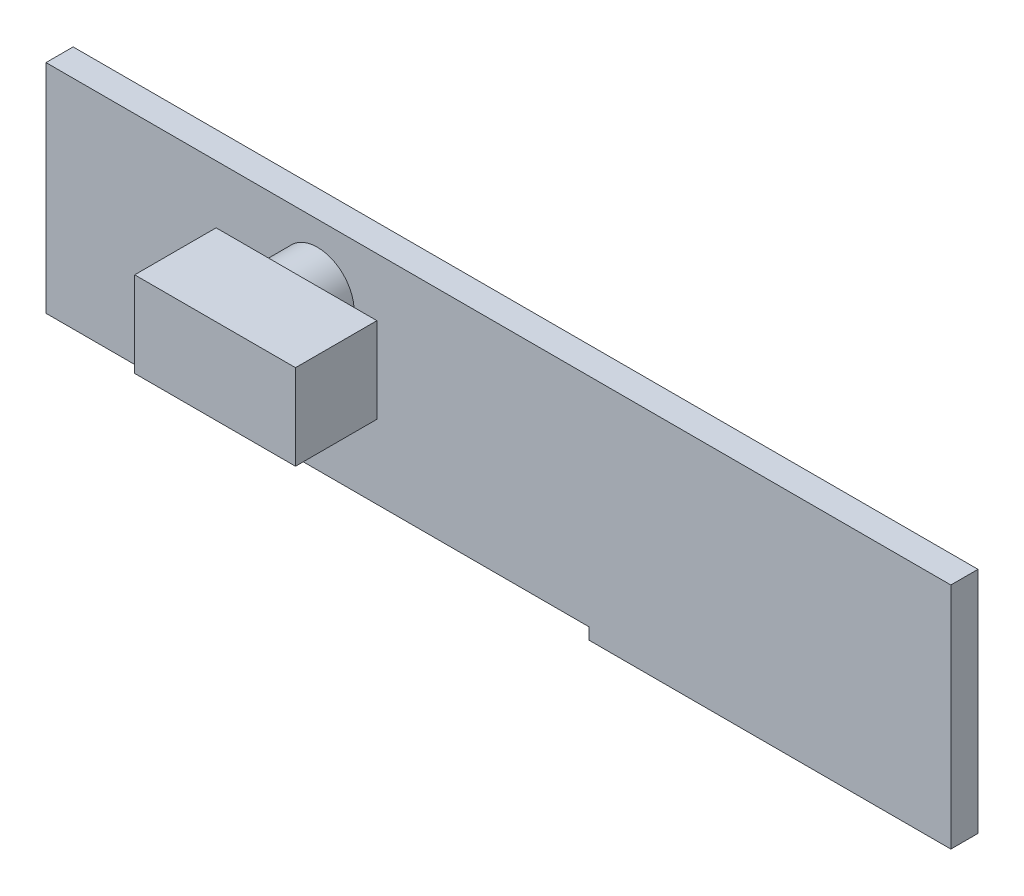
SolidWorks part; units mm, degrees
ref_plane "Front Plane" through (0, 0, 0) normal (0, 0, 1) x (1, 0, 0)
ref_plane "Top Plane" through (0, 0, 0) normal (0, 1, 0) x (1, 0, 0)
ref_plane "Right Plane" through (0, 0, 0) normal (1, 0, 0) x (0, 0, -1)
sketch "Sketch2" plane through (0, 0, 0) normal (0, 0, 1) x (1, 0, 0)
  line L1 (-47.8692, 21.2481) -> (206.1308, 21.2481)
  line L2 (-47.8692, 21.2481) -> (-47.8692, 8.5481)
  line L3 (-47.8692, 8.5481) -> (206.1308, 8.5481)
  line L4 (206.1308, 21.2481) -> (206.1308, 8.5481)
  dimension "D1" = 12.7
  dimension "D2" = 254
extrude "Boss-Extrude1" add sketch "Sketch2" along normal blind 101.6
sketch "Sketch3" plane through (0, 21.2481, 0) normal (0, 1, 0) x (1, 0, 0)
  circle A0 centre (79.1308, -28.4831) radius 17.1408
extrude "Boss-Extrude2" add sketch "Sketch3" along normal blind 19.05
sketch "Sketch4" plane through (0, 40.2981, 0) normal (0, 1, 0) x (1, 0, 0)
  line L1 (50.7675, -8.111) -> (126.0034, -8.111)
  line L2 (50.7675, -8.111) -> (50.7675, -48.0661)
  line L3 (50.7675, -48.0661) -> (126.0034, -48.0661)
  line L4 (126.0034, -8.111) -> (126.0034, -48.0661)
extrude "Boss-Extrude3" add sketch "Sketch4" along normal blind 38.1
scale "Scale2" scale about centroid uniform scaling yes scale factor 0.06
move or copy body "rotate" bodies to move or copy 105 copy no rotation origin (0, 33.6669, 26.5501) rotation axis (1, 0, 0) rotation angle 90
scale "Scale5" scale about centroid uniform scaling yes scale factor 0.25
move or copy body "-4 x" bodies to move or copy 111 copy no translate (-101.6, 0, 0)
move or copy body "-2 y" bodies to move or copy 117 copy no translate (0, -55.88, 0)
scale "Scale6" bodies to scale 121 scale about centroid uniform scaling yes scale factor 0.25
move or copy body "-2.1z" bodies to move or copy 122 copy no translate (0, 0, -30.48)
sketch "Sketch6" plane through (0, -39.7871, 0) normal (0, 1, 0) x (1, 0, 0)
  line L1 (-19.6967, 11.0887) -> (-19.0617, 11.0887)
  line L2 (-19.6967, 11.0887) -> (-19.6967, 11.0411)
  line L3 (-19.6967, 11.0411) -> (-19.0617, 11.0411)
  line L4 (-19.0617, 11.0887) -> (-19.0617, 11.0411)
  dimension "D1" = 0.635
extrude "Boss-Extrude6" add sketch "Sketch6" against normal blind 0.4013
